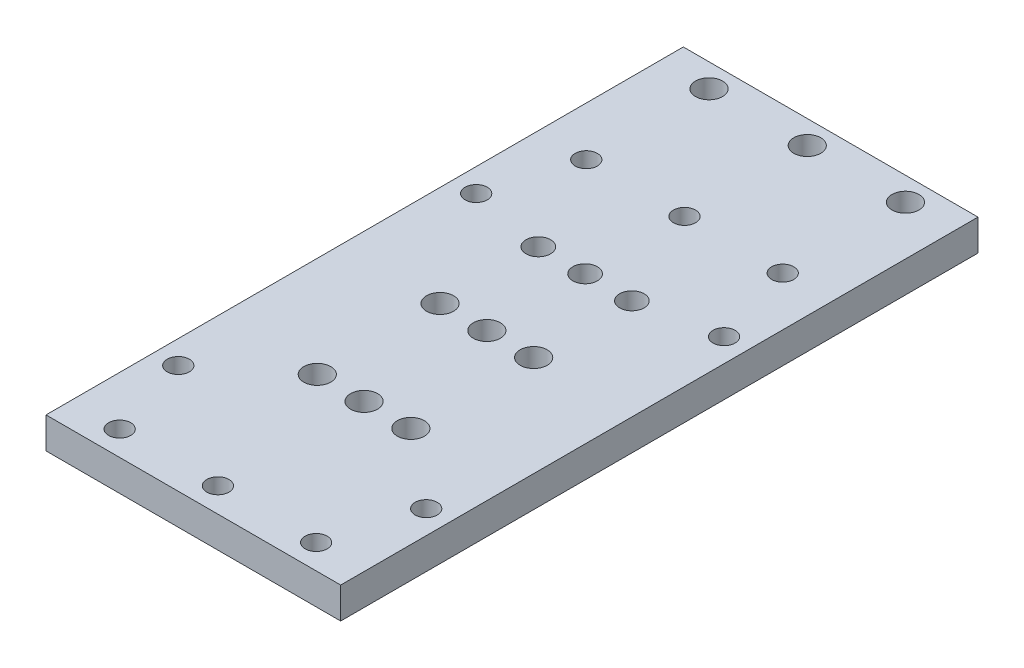
SolidWorks part; units mm, degrees
material "6061 Alloy"
ref_plane "Front Plane" through (0, 0, 0) normal (0, 0, 1) x (1, 0, 0)
ref_plane "Top Plane" through (0, 0, 0) normal (0, 1, 0) x (1, 0, 0)
ref_plane "Right Plane" through (0, 0, 0) normal (1, 0, 0) x (0, 0, -1)
sketch "Sketch1" plane through (0, 0, 0) normal (0, 1, 0) x (1, 0, 0)
  line L1 (-30, 80) -> (30, 80)
  line L2 (-30, 80) -> (-30, -80)
  line L3 (-30, -80) -> (30, -80)
  line L4 (30, 80) -> (30, -80)
  line L5 (0, -80) -> (0, 80) construction
  line L6 (-30, 0) -> (30, 0) construction
  point P0 (0, 0)
  dimension "D1" = 60
  dimension "D2" = 160
extrude "Boss-Extrude1" add sketch "Sketch1" along normal mid plane 6.35
sketch "Sketch3" plane through (0, 0, 0) normal (0, 1, 0) x (1, 0, 0)
  line L0 (0, 75.2375) -> (20, 75.2375) construction
  line L5 (0, -80) -> (0, 80) construction
  line L6 (-30, 0) -> (30, 0) construction
  line L7 (0, 50.2375) -> (20, 50.2375) construction
  line L8 (30, 80) -> (-30, 80) construction
  line L9 (-30, 80) -> (-30, -80) construction
  line L10 (-30, -80) -> (30, -80) construction
  line L11 (30, -80) -> (30, 80) construction
  line L12 (0, -44.7625) -> (20, -44.7625) construction
  circle A0 centre (20, 75.2375) radius 2.75
  circle A1 centre (20, 50.2375) radius 2.25
  circle A2 centre (-20, 50.2375) radius 2.25
  circle A3 centre (-20, 75.2375) radius 2.75
  circle A4 centre (0, 75.2375) radius 2.75
  circle A5 centre (0, 50.2375) radius 2.25
  circle A6 centre (20, -44.7625) radius 2.25
  circle A7 centre (-20, -44.7625) radius 2.25
  circle A8 centre (0, -44.7625) radius 2.25
  point P0 (0, 0)
  dimension "D4" = 5.5
  dimension "D5" = 4.5
  dimension "D1" = 4.7625
  dimension "D2" = 25
  dimension "D3" = 20
  dimension "D6" = 2
extrude "M4/5_through" cut sketch "Sketch3" against normal up to surface (3.175 mm away) and the other way blind 6.35 up to face at (0, -3.175, 0)
sketch "Sketch4" plane through (0, 0, -80) normal (0, 0, -1) x (-1, 0, 0)
  line L0 (0, 0) -> (-12, 0) construction
  line L1 (0, 0) -> (0, 3.175) construction
  line L2 (-30, 3.175) -> (30, 3.175) construction
  circle A0 centre (-12, 0) radius 1.5
  circle A1 centre (12, 0) radius 1.5
  dimension "D1" = 3
  dimension "D2" = 12
extrude "M3_DRILL" cut sketch "Sketch4" against normal blind 8
sketch "Sketch5" plane through (0, 3.175, 0) normal (0, 1, 0) x (1, 0, 0)
  line L0 (-20, -44.7625) -> (0, -44.7625) construction
  line L1 (-30, 80) -> (-30, -80) construction
  line L2 (0, 0) -> (0, -23.6676) construction
  line L3 (-20, 50.2375) -> (-20, -44.7625) construction
  line L4 (-20, 2.7375) -> (-9.1233, 2.7375) construction
  circle A0 centre (-25.2375, -27.5875) radius 2.25
  circle A1 centre (25.2375, -27.5875) radius 2.25
  circle A2 centre (25.2375, 33.0625) radius 2.25
  circle A3 centre (-25.2375, 33.0625) radius 2.25
  dimension "D2" = 4.5
  dimension "D1" = 17.175
  dimension "D3" = 4.7625
extrude "M4_through" cut sketch "Sketch5" against normal up to surface (6.35 mm away) up to face at (20, -3.175, -47.9875)
sketch "Sketch6" plane through (0, 3.175, 0) normal (0, 1, 0) x (1, 0, 0)
  line L0 (0, 0) -> (0, -64.4319) construction
  circle A0 centre (0, 30) radius 2.5
  circle A1 centre (9.53, 30) radius 2.5
  circle A2 centre (-9.53, 30) radius 2.5
  dimension "D1" = 5
  dimension "D4" = 30
  dimension "D2" = 2
  dimension "D3" = 2
extrude "M5_DRILL" cut sketch "Sketch6" against normal up to surface (6.35 mm away) up to face at (-25.2375, -3.175, -30.8125)
sketch "Sketch7" plane through (0, 3.175, 0) normal (0, 1, 0) x (1, 0, 0)
  line L0 (0, 30) -> (0, -15) construction
  circle A0 centre (0, 10) radius 2.75
  circle A1 centre (0, -15) radius 2.75
  circle A2 centre (9.53, 10) radius 2.75
  circle A3 centre (9.53, -15) radius 2.75
  circle A4 centre (-9.53, 10) radius 2.75
  circle A5 centre (-9.53, -15) radius 2.75
  dimension "D3" = 5.5
  dimension "D1" = 45
  dimension "D2" = 20
  dimension "D4" = 2
  dimension "D5" = 2
extrude "M5_through" cut sketch "Sketch7" against normal up to surface (6.35 mm away) up to face at (-9.53, -3.175, -27.5)
sketch "Sketch8" plane through (0, 3.175, 0) normal (0, 1, 0) x (1, 0, 0)
  line L0 (-20, -44.7625) -> (20, -44.7625) construction
  line L1 (30, -80) -> (30, 80) construction
  line L2 (-30, -80) -> (30, -80)
  line L3 (-30, -80) -> (-30, -49.7625)
  line L4 (-30, -49.7625) -> (30, -49.7625)
  line L5 (30, -80) -> (30, -49.7625)
  line L6 (0, -49.7625) -> (0, -80) construction
  line L7 (-30, -64.8812) -> (30, -64.8812) construction
  point P260 (0, -64.8812)
  dimension "D1" = 5
extrude "Cut-Extrude3" cut sketch "Sketch8" against normal up to surface (6.35 mm away) up to face at (-9.53, -3.175, -7.25)
